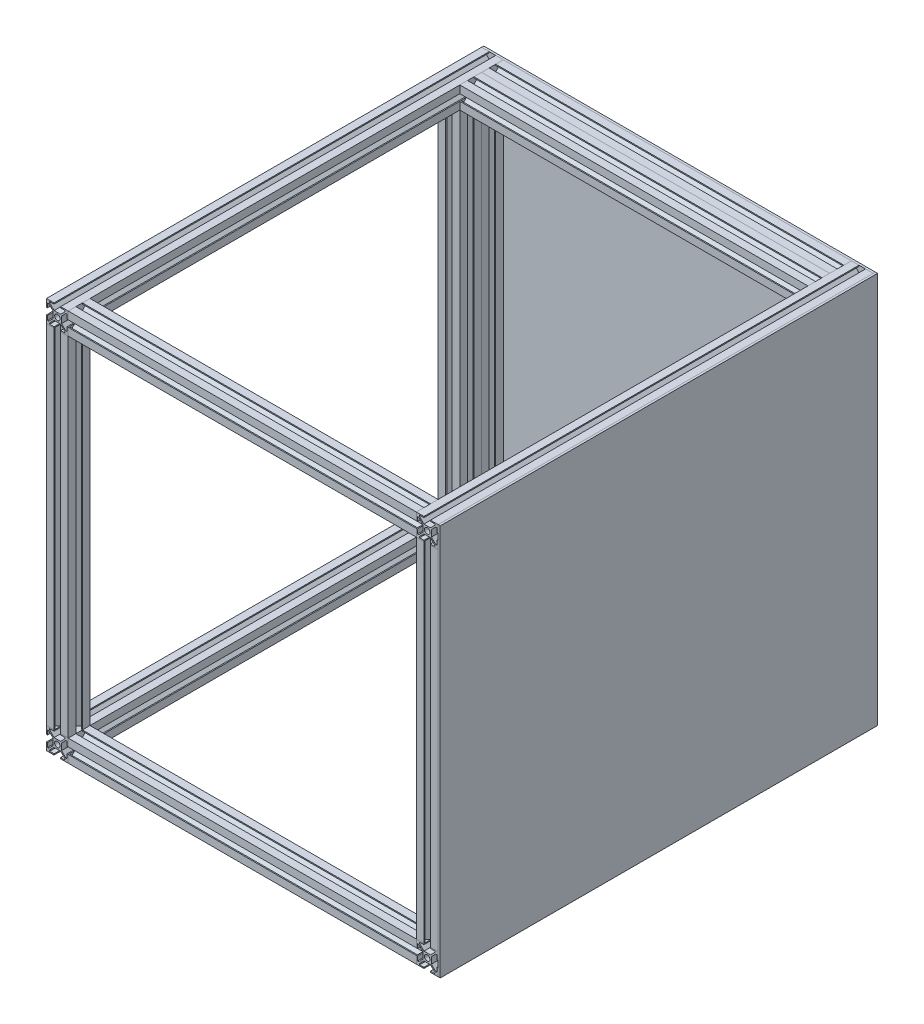
SolidWorks part; units mm, degrees
material "6063-T1"
ref_plane "Front Plane" through (0, 0, 0) normal (1, 0, 0) x (0, 1, 0)
ref_plane "Top Plane" through (0, 0, 0) normal (0, 0, 1) x (0, 1, 0)
ref_plane "Right Plane" through (0, 0, 0) normal (0, 1, 0) x (-1, 0, 0)
ref_axis "Axis1" through (0, 0, 0) along (0, 0, 1)
sketch "Sketch2" plane through (0, 0, 0) normal (1, 0, 0) x (0, 1, 0)
  line L5 (-180, 3) -> (-180, 10)
  line L67 (-180, 10) -> (-160, 10) construction
  line L68 (-180, 10) -> (-180, -10) construction
  line L69 (-180, -10) -> (-160, -10) construction
  line L70 (-160, 10) -> (-160, -10) construction
  line L72 (-160, 0) -> (160, 0) construction
  line L73 (-180, 10) -> (-173, 10)
  line L74 (-173, 10) -> (-173, 9)
  line L75 (-173, 9) -> (-177, 9)
  line L76 (-177, 9) -> (-177, 7.9857)
  line L77 (-177, 7.9857) -> (-173, 3.9857)
  line L78 (-173, 3.9857) -> (-170, 3.9857)
  line L79 (-180, 3) -> (-179, 3)
  line L80 (-179, 3) -> (-179, 7)
  line L81 (-179, 7) -> (-177.9857, 7)
  line L82 (-177.9857, 7) -> (-173.9857, 3)
  line L83 (-173.9857, 3) -> (-173.9857, 0)
  line L84 (-173.9857, 3) -> (-173, 3.9857) construction
  line L85 (-167, 10) -> (-160, 10)
  line L86 (-160, 10) -> (-160, 3)
  line L87 (-160, 3) -> (-161, 3)
  line L88 (-161, 3) -> (-161, 7)
  line L89 (-161, 7) -> (-162.0143, 7)
  line L90 (-162.0143, 7) -> (-166.0143, 3)
  line L91 (-166.0143, 3) -> (-166.0143, 0)
  line L92 (-167, 10) -> (-167, 9)
  line L93 (-167, 9) -> (-163, 9)
  line L94 (-163, 9) -> (-163, 7.9857)
  line L95 (-163, 7.9857) -> (-167, 3.9857)
  line L96 (-167, 3.9857) -> (-170, 3.9857)
  line L97 (-167, 3.9857) -> (-166.0143, 3) construction
  line L98 (-160, -3) -> (-160, -10)
  line L99 (-160, -10) -> (-167, -10)
  line L100 (-167, -10) -> (-167, -9)
  line L101 (-167, -9) -> (-163, -9)
  line L102 (-163, -9) -> (-163, -7.9857)
  line L103 (-163, -7.9857) -> (-167, -3.9857)
  line L104 (-167, -3.9857) -> (-170, -3.9857)
  line L105 (-160, -3) -> (-161, -3)
  line L106 (-161, -3) -> (-161, -7)
  line L107 (-161, -7) -> (-162.0143, -7)
  line L108 (-162.0143, -7) -> (-166.0143, -3)
  line L109 (-166.0143, -3) -> (-166.0143, 0)
  line L110 (-166.0143, -3) -> (-167, -3.9857) construction
  line L111 (-173, -10) -> (-180, -10)
  line L112 (-180, -10) -> (-180, -3)
  line L113 (-180, -3) -> (-179, -3)
  line L114 (-179, -3) -> (-179, -7)
  line L115 (-179, -7) -> (-177.9857, -7)
  line L116 (-177.9857, -7) -> (-173.9857, -3)
  line L117 (-173.9857, -3) -> (-173.9857, 0)
  line L118 (-173, -10) -> (-173, -9)
  line L119 (-173, -9) -> (-177, -9)
  line L120 (-177, -9) -> (-177, -7.9857)
  line L121 (-177, -7.9857) -> (-173, -3.9857)
  line L122 (-173, -3.9857) -> (-170, -3.9857)
  line L123 (-173, -3.9857) -> (-173.9857, -3) construction
  circle A0 centre (-170, 0) radius 2.5
  point P0 (-192.5803, 22.4509)
  point P6 (0, 0)
  point P9 (0, 0)
  point P10 (-162.6206, -0.6265)
  point P33 (-162.5743, -0.6264)
  point P46 (-173.9654, 0.3965)
  point P55 (-160, 0)
  point P72 (-160, 0)
  point P107 (-170, 0)
  dimension "D5" = 5
  dimension "D1" = 20
  dimension "D2" = 45
  dimension "D4" = 6
  dimension "D3" = 14
  dimension "D8" = 45
  dimension "D7" = 1
  dimension "D6" = 4
sketch "Sketch1" plane through (0, 0, 0) normal (0, 0, 1) x (0, 1, 0)
  line L0 (-160, 160) -> (160, -160) construction
  line L5 (-160, 160) -> (160, 160)
  line L6 (-160, 160) -> (-160, -160)
  line L7 (-160, -160) -> (160, -160)
  line L8 (160, 160) -> (160, -160)
  point P108 (0, 0)
  dimension "D1" = 320
  dimension "D2" = 320
sweep "Aluminium Extrsion Base" add profiles "Sketch2" path "Sketch1"
pattern_circular "CirPattern1" count 4 over 360 about axis through (0, 0, 0) along (0, 0, 1) of "Aluminium Extrsion Base"
mirror "Mirror5" about plane through (-160, 167, 10) normal (0, 0, -1) of bodies 122 118 124 123
sketch "Sketch4" plane through (0, 0, -10) normal (0, 0, 1) x (0, 1, 0)
  line L5 (-180, -167) -> (-180, -160)
  line L67 (-180, -160) -> (-160, -160) construction
  line L68 (-180, -160) -> (-180, -180) construction
  line L69 (-180, -180) -> (-160, -180) construction
  line L70 (-160, -160) -> (-160, -180) construction
  line L71 (-160, -167) -> (-160, -170) construction
  line L73 (-180, -160) -> (-173, -160)
  line L74 (-173, -160) -> (-173, -161)
  line L75 (-173, -161) -> (-177, -161)
  line L76 (-177, -161) -> (-177, -162.0896)
  line L77 (-177, -162.0896) -> (-173, -166.0896)
  line L78 (-173, -166.0896) -> (-170, -166.0896)
  line L79 (-180, -167) -> (-179, -167)
  line L80 (-179, -167) -> (-179, -163)
  line L81 (-179, -163) -> (-177.9104, -163)
  line L82 (-177.9104, -163) -> (-173.9104, -167)
  line L83 (-173.9104, -167) -> (-173.9104, -170)
  line L84 (-173.9104, -167) -> (-173, -166.0896) construction
  line L85 (-167, -160) -> (-160, -160)
  line L86 (-160, -160) -> (-160, -167)
  line L87 (-160, -167) -> (-161, -167)
  line L88 (-161, -167) -> (-161, -163)
  line L89 (-161, -163) -> (-162.0896, -163)
  line L90 (-162.0896, -163) -> (-166.0896, -167)
  line L91 (-166.0896, -167) -> (-166.0896, -170)
  line L92 (-167, -160) -> (-167, -161)
  line L93 (-167, -161) -> (-163, -161)
  line L94 (-163, -161) -> (-163, -162.0896)
  line L95 (-163, -162.0896) -> (-167, -166.0896)
  line L96 (-167, -166.0896) -> (-170, -166.0896)
  line L97 (-167, -166.0896) -> (-166.0896, -167) construction
  line L98 (-160, -173) -> (-160, -180)
  line L99 (-160, -180) -> (-167, -180)
  line L100 (-167, -180) -> (-167, -179)
  line L101 (-167, -179) -> (-163, -179)
  line L102 (-163, -179) -> (-163, -177.9104)
  line L103 (-163, -177.9104) -> (-167, -173.9104)
  line L104 (-167, -173.9104) -> (-170, -173.9104)
  line L105 (-160, -173) -> (-161, -173)
  line L106 (-161, -173) -> (-161, -177)
  line L107 (-161, -177) -> (-162.0896, -177)
  line L108 (-162.0896, -177) -> (-166.0896, -173)
  line L109 (-166.0896, -173) -> (-166.0896, -170)
  line L110 (-166.0896, -173) -> (-167, -173.9104) construction
  line L111 (-173, -180) -> (-180, -180)
  line L112 (-180, -180) -> (-180, -173)
  line L113 (-180, -173) -> (-179, -173)
  line L114 (-179, -173) -> (-179, -177)
  line L115 (-179, -177) -> (-177.9104, -177)
  line L116 (-177.9104, -177) -> (-173.9104, -173)
  line L117 (-173.9104, -173) -> (-173.9104, -170)
  line L118 (-173, -180) -> (-173, -179)
  line L119 (-173, -179) -> (-177, -179)
  line L120 (-177, -179) -> (-177, -177.9104)
  line L121 (-177, -177.9104) -> (-173, -173.9104)
  line L122 (-173, -173.9104) -> (-170, -173.9104)
  line L123 (-173, -173.9104) -> (-173.9104, -173) construction
  line L124 (-167, -160) -> (-170, -160) construction
  circle A0 centre (-170, -170) radius 2.5
  point P0 (-192.5803, 22.4509)
  point P6 (0, 0)
  point P9 (0, 0)
  point P10 (-162.6206, -0.6265)
  point P33 (-162.5743, -0.6264)
  point P46 (-173.9654, 0.3965)
  point P55 (-160, 0)
  point P59 (-170.799, -170.6795)
  point P72 (-160, -170)
  point P107 (-170, -170)
  dimension "D2" = 45
  dimension "D5" = 5
  dimension "D1" = 20
  dimension "D3" = 14
  dimension "D4" = 6
  dimension "D7" = 1
  dimension "D8" = 45
  dimension "D6" = 4
extrude "Aluminium Extrusion Pillar" add sketch "Sketch4" along normal blind 400 separate body
pattern_circular "CirPattern2" count 4 over 360 about axis through (0, 0, 0) along (0, 0, 1) of bodies 125
ref_plane "Plane2" through (0, 0, 190) normal (0, 0, 1) x (1, 0, 0)
mirror "Mirror4" about plane through (0, 0, 190) normal (0, 0, 1) of bodies 124 118 122 123
sketch "Sketch5" plane through (0, 0, -10) normal (0, 0, -1) x (1, 0, 0)
  line L1 (-180, 180) -> (180, 180)
  line L2 (-180, 180) -> (-180, -180)
  line L3 (-180, -180) -> (180, -180)
  line L4 (180, 180) -> (180, -180)
  line L5 (0, -180) -> (0, 180) construction
  line L6 (-180, 0) -> (180, 0) construction
  circle A0 centre (-170, -170) radius 2.5 construction
  circle A1 centre (170, -170) radius 2.5 construction
  circle A2 centre (170, 170) radius 2.5 construction
  circle A3 centre (-170, 170) radius 2.5 construction
  circle A4 centre (-170, -170) radius 2.5
  circle A5 centre (170, -170) radius 2.5
  circle A6 centre (170, 170) radius 2.5
  circle A7 centre (-170, 170) radius 2.5
  point P308 (0, 0)
extrude "Bottom Plate" add sketch "Sketch5" along normal blind 2 separate body
sketch "Sketch6" plane through (180, 0, 0) normal (1, 0, 0) x (0, 1, 0)
  line L1 (-180, 390) -> (180, 390)
  line L2 (-180, 390) -> (-180, -12)
  line L3 (-180, -12) -> (180, -12)
  line L4 (180, 390) -> (180, -12)
  line L5 (0, -12) -> (0, 390) construction
  line L6 (-180, 189) -> (180, 189) construction
  point P4 (0, 0)
  point P5 (0, 0)
  point P6 (0, 0)
  point P96 (0, 189)
extrude "Back Plate" add sketch "Sketch6" along normal blind 2 separate body
equation "\"extrusion_width\"= 20mm"
equation "\"frame_height\"= 360mm"
equation "\"frame_width\"= 320mm"
equation "\"frame_length\"= 320mm"
equation "\"bed_radius\"= 100mm"
equation "\"bottom_plate_thickness\"=2"
equation "\"D2@Sketch1\"=\"frame_length\""
equation "\"D1@Sketch1\"=\"frame_width\""
equation "\"D1@Sketch2\"=\"extrusion_width\""
equation "\"D1@Aluminium Extrusion Pillar\" = \"frame_height\" + \"extrusion_width\" * 2"
equation "\"D1@Bottom Plate\" = \"bottom_plate_thickness\""
